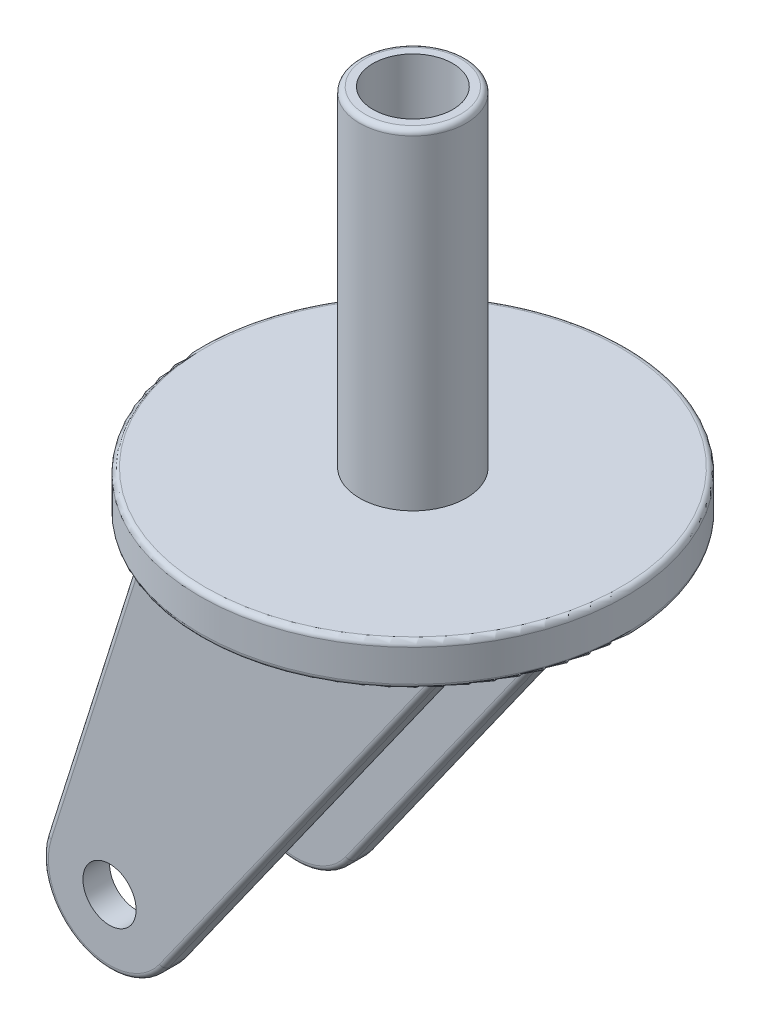
SolidWorks part; units mm, degrees
ref_plane "Front Plane" through (0, 0, 0) normal (0, 0, 1) x (1, 0, 0)
ref_plane "Top Plane" through (0, 0, 0) normal (0, 1, 0) x (1, 0, 0)
ref_plane "Right Plane" through (0, 0, 0) normal (1, 0, 0) x (0, 0, -1)
sketch "Sketch1" plane through (0, 0, 0) normal (0, 1, 0) x (1, 0, 0)
  circle A0 centre (0, 0) radius 40
  dimension "D1" = 80
extrude "Boss-Extrude1" add sketch "Sketch1" along normal blind 8
fillet "Fillet1" radius 1 2 edges at (0, 0, 40) (0, 8, 40)
ref_plane "Plane1" through (0, 0, 15) normal (0, 0, 1) x (1, 0, 0)
sketch "Sketch4" plane through (0, 0, 15) normal (0, 0, 1) x (1, 0, 0)
  line L0 (0, 0) -> (28, 0)
  line L1 (-39, 0) -> (39, 0) construction
  line L2 (0, 0) -> (-28, 0)
  line L3 (28, 0) -> (-26.8058, -77.2339)
  line L4 (-28, 0) -> (-48.9196, -66.2353)
  arc A0 (-48.9196, -66.2353) -> (-26.8058, -77.2339) centre (-37, -70) ccw
  circle A1 centre (-37, -70) radius 5
  dimension "D3" = 25
  dimension "D6" = 10
  dimension "D1" = 28
  dimension "D2" = 28
  dimension "D4" = 70
  dimension "D5" = 65
extrude "Boss-Extrude2" add sketch "Sketch4" along normal blind 5
fillet "Fillet5" radius 1 6 edges at (0.5971, -38.6169, 20) (0.5971, -38.6169, 15) (-42.5665, -81.1921, 15) (-42.5665, -81.1921, 20) (-38.4598, -33.1177, 20) (-38.4598, -33.1177, 15)
fillet "Fillet6" radius 2 8 edges at (-27.6928, 0, 15.2929) (-27.6928, 0, 19.7071) (-28, 0, 17.5) (-0.0887, 0, 15) (27.6409, 0, 15.2929) (27.6409, 0, 19.7071) (28, 0, 17.5) (-0.0887, 0, 20)
mirror "Mirror1" about plane through (0, 0, 0) normal (0, 0, 1) of "Fillet6", "Fillet5", "Boss-Extrude2"
sketch "Sketch5" plane through (0, 0, 0) normal (0, 1, 0) x (1, 0, 0)
  circle A0 centre (0, 0) radius 10
  circle A1 centre (0, 0) radius 7.5
  dimension "D1" = 15
  dimension "D2" = 20
extrude "Boss-Extrude3" add sketch "Sketch5" along normal blind 70
fillet "Fillet7" radius 1 1 edges at (0, 70, 10)
